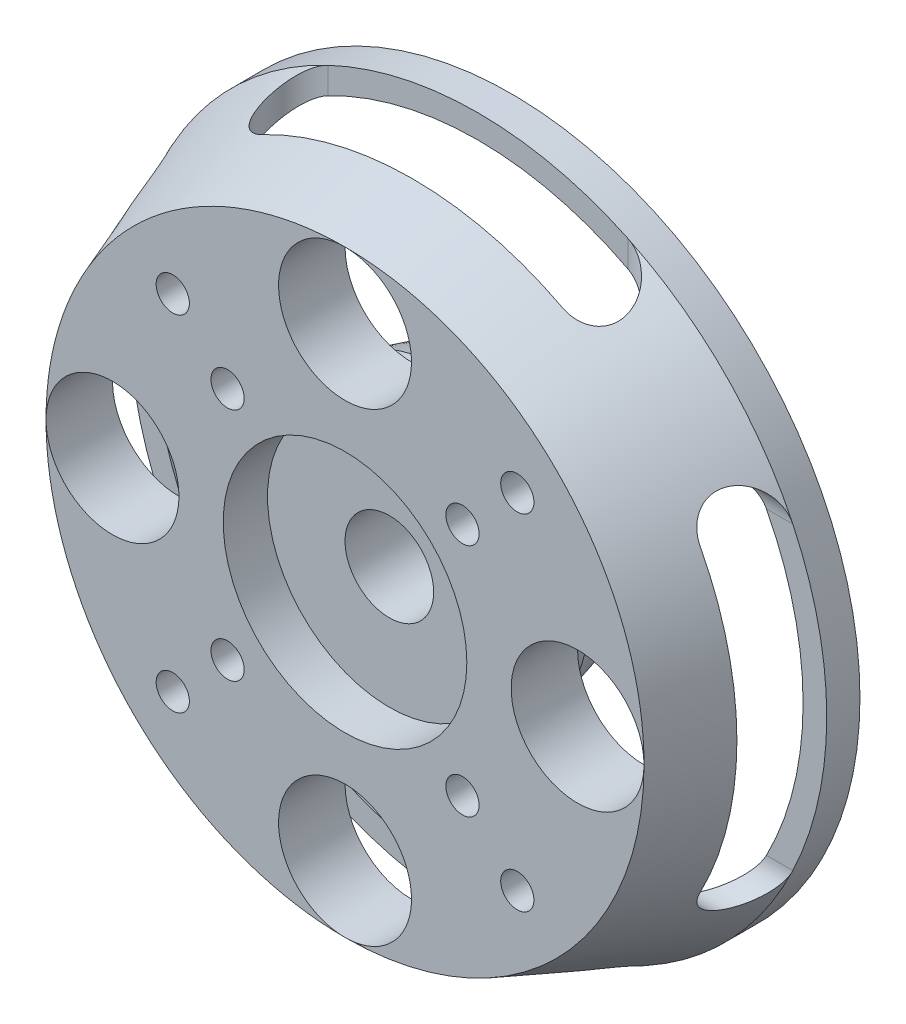
SolidWorks part; units mm, degrees
ref_plane "Front Plane" through (0, 0, 0) normal (0, 0, 1) x (1, 0, 0)
ref_plane "Top Plane" through (0, 0, 0) normal (0, 1, 0) x (1, 0, 0)
ref_plane "Right Plane" through (0, 0, 0) normal (1, 0, 0) x (0, 0, -1)
ref_axis "Z" through (0, 0, -15.75) along (0, 0, 1)
sketch "Sketch1" plane through (0, 0, 0) normal (0, 1, 0) x (1, 0, 0)
  line L0 (29.5, 15) -> (29.5, 12.3627)
  line L1 (29.5, 12.3627) -> (27.114, 6)
  line L2 (27.114, 6) -> (13, 6)
  line L3 (13, 6) -> (13, 9)
  line L4 (11.3923, 15) -> (4, 15)
  line L5 (4, 15) -> (4, 4)
  line L6 (11, 0) -> (27, 0)
  line L7 (27, 0) -> (31.5, 12)
  line L8 (31.5, 12) -> (31.5, 15)
  line L9 (31.5, 15) -> (29.5, 15)
  line L10 (0, -76.8889) -> (0, 67.6055) construction
  line L11 (11, 0) -> (11, 4)
  line L12 (11, 4) -> (4, 4)
  line L13 (4, 4) -> (4, 0) construction
  line L14 (4, 0) -> (11, 0) construction
  line L15 (11.3923, 15) -> (13, 9)
  line L16 (13, 15) -> (11.3923, 15) construction
  line L17 (13, 9) -> (13, 15) construction
  dimension "D1" = 8
  dimension "D2" = 15
  dimension "D3" = 2
  dimension "D4" = 3
  dimension "D5" = 2
  dimension "D6" = 63
  dimension "D7" = 6
  dimension "D8" = 9
  dimension "D9" = 54
  dimension "D10" = 22
  dimension "D11" = 4
  dimension "D12" = 15
  dimension "D13" = 3
revolve "Revolve1" add sketch "Sketch1" angle 360 about L10
ref_plane "Plane4" through (-31.5, 0, 0) normal (-1, 0, 0) x (0, 0, 1)
sketch "Sketch2" plane through (-31.5, 0, 0) normal (-1, 0, 0) x (0, 0, 1)
  line L0 (-9.05, -13.55) -> (-9.05, 13.55) construction
  line L1 (-12, -13.55) -> (-12, 13.55)
  line L2 (-6.1, -13.55) -> (-6.1, 13.55)
  line L3 (-15.75, 0) -> (0.75, 0) construction
  line L4 (-12.4387, -16.5) -> (-5.6613, -16.5) construction
  line L5 (-12.4387, 16.5) -> (-5.6613, 16.5) construction
  line L7 (-15, 29.5) -> (-15, -29.5) construction
  arc A0 (-12, -13.55) -> (-6.1, -13.55) centre (-9.05, -13.55) ccw
  arc A1 (-6.1, 13.55) -> (-12, 13.55) centre (-9.05, 13.55) ccw
  point P2 (-9.05, 0)
  dimension "D2" = 33
  dimension "D1" = 5.9
  dimension "D3" = 3
extrude "Cut-Extrude1" cut sketch "Sketch2" against normal blind 10
pattern_circular "CirPattern1" count 4 over 360 about axis through (0, 0, -15.75) along (0, 0, 1) of "Cut-Extrude1"
sketch "Sketch3" plane through (0, 0, 0) normal (0, 0, 1) x (1, 0, 0)
  line L0 (-21, 0) -> (0, 0) construction
  line L1 (0, 0) -> (-15.5563, 15.5563) construction
  circle A0 centre (-21, 0) radius 6
  circle A1 centre (0, 21) radius 6
  circle A2 centre (21, 0) radius 6
  circle A3 centre (0, -21) radius 6
  circle A4 centre (-15.5563, 15.5563) radius 1.5
  circle A5 centre (-10.6066, 10.6066) radius 1.5
  circle A6 centre (10.6066, 10.6066) radius 1.5
  circle A7 centre (15.5563, 15.5563) radius 1.5
  circle A8 centre (10.6066, -10.6066) radius 1.5
  circle A9 centre (15.5563, -15.5563) radius 1.5
  circle A10 centre (-10.6066, -10.6066) radius 1.5
  circle A11 centre (-15.5563, -15.5563) radius 1.5
  point P13 (0, 0)
  point P31 (0, 0)
  dimension "D1" = 12
  dimension "D5" = 3
  dimension "D2" = 21
  dimension "D4" = 45
  dimension "D6" = 7
  dimension "D7" = 15
  dimension "D3" = 4
  dimension "D8" = 4
extrude "Cut-Extrude2" cut sketch "Sketch3" against normal through all
equation "\"RotorMainLength\"= 41'rotor body longest dimension"
equation "\"OverallLength\"= 65.8'The height of the whole motor, not counting shaft protrusions"
equation "\"RotorDiameter\"= 63'Overall rotor diameter"
equation "\"RotorTopCapHeight\"= 14'Rough measurement/eyeballed. Not super critical for this; most important dim is overall length"
equation "\"RotorLargeHoleDiameter\"= 17'ID measurement with calipers"
equation "\"RotorLargeHoleTangentSpacing\"= 19'tangent to tangent on the large holes. add one diameter to achieve the center distances"
equation "\"RotorLargeHoleCenterDistance\"= \"RotorLargeHoleTangentSpacing\" + \"RotorLargeHoleDiameter\"'Center to center spacing for large hole"
equation "\"RotorSmallHoleID\"= 8'ID measurement with calipers"
equation "\"RotorSmallHoleTangentSpacing\"= 37'Tangent to Tangent (rounded to the nearest integer, real measurement was like 0.03mm off)"
equation "\"RotorSmallHoleCenterDistance\"= \"RotorSmallHoleID\" + \"RotorSmallHoleTangentSpacing\"'Center to center spacing for small holes"
equation "\"ShaftDiameter\"= 8"
equation "\"RotorShaftTopCapDiameter\"= 18'the small circular extrusion at the top of the rotor"
equation "\"RotorShaftTopCapHeight\"= 2'Height of the small cylindircal extrusion at the top of the rotor"
equation "\"RotorBoltCircleFlatDiameter\"= 30'Diameter of the flat portion where the bolt circle is drilled in the rotor"
equation "\"RotorTaperedEdgeHeight\"= 7'approximate, vertical distance of the tapered/angled edge of the rotor"
equation "\"RotorBoltCircleCenterDistance\"= 23mm'rounded, hard to measure with calipers so assuming they aren't fucking insane and chose this"
equation "\"StatorTrayHeight\"= 3+6+6\t'Rough measurement/eyeballed. Not super critical. Take up clearance in airgap; maintain overall height"
equation "\"D1@Sketch1\"=\"ShaftDiameter\""
equation "\"D2@Sketch1\"=\"StatorTrayHeight\""
equation "\"D6@Sketch1\"=\"RotorDiameter\""
equation "\"D9@Sketch1\"=54"
equation "\"D7@Sketch3\"=15"
equation "\"D6@Sketch3\"=7"
equation "\"D1@Sketch3\"=12"
